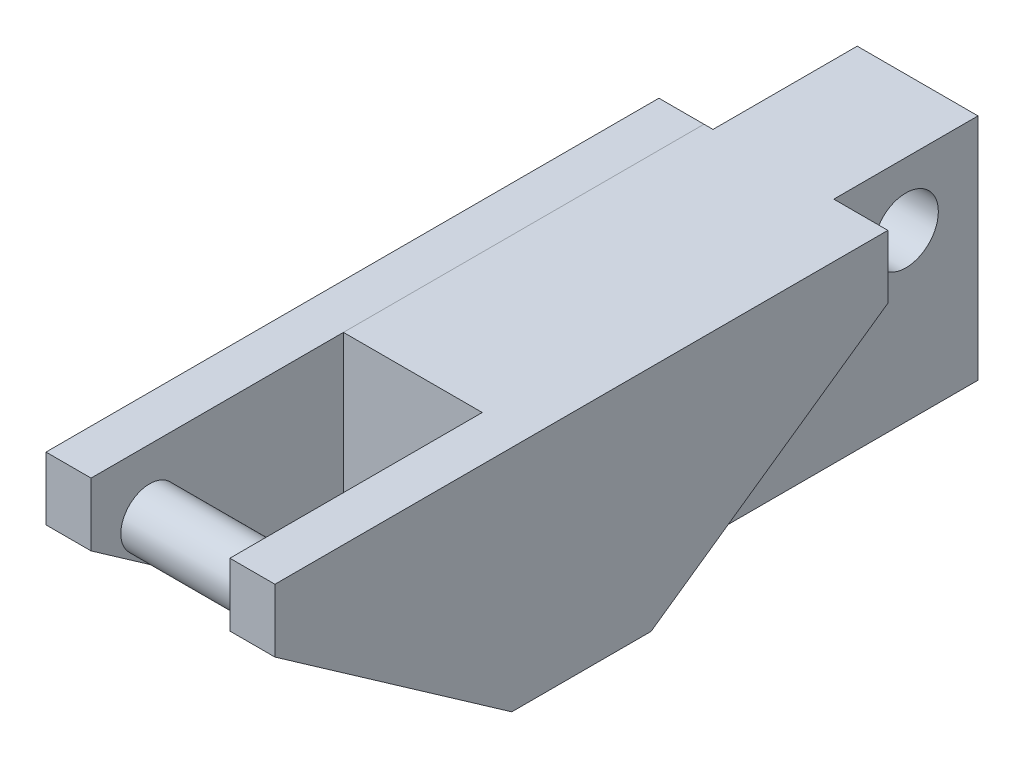
SolidWorks part; units mm, degrees
ref_plane "Front Plane" through (0, 0, 0) normal (0, 0, 1) x (1, 0, 0)
ref_plane "Top Plane" through (0, 0, 0) normal (0, 1, 0) x (1, 0, 0)
ref_plane "Right Plane" through (0, 0, 0) normal (1, 0, 0) x (0, 0, -1)
sketch "Sketch2" plane through (0, 0, 0) normal (0, 1, 0) x (1, 0, 0)
  line L0 (-31.2782, 15.5442) -> (-18.5782, 15.5442)
  line L1 (-28.2782, 23.5442) -> (-21.5782, 23.5442)
  line L2 (-31.2782, 15.5442) -> (-31.2782, -18.4558)
  line L3 (-31.2782, -18.4558) -> (-28.7782, -18.4558)
  line L4 (-18.5782, 15.5442) -> (-18.5782, -18.4558)
  line L5 (-28.2782, 23.5442) -> (-28.2782, 15.5442)
  line L6 (-21.5782, 23.5442) -> (-21.5782, 15.5442)
  line L7 (-28.7782, -18.4558) -> (-28.7782, -4.4558)
  line L8 (-28.7782, -4.4558) -> (-21.0782, -4.4558)
  line L9 (-21.0782, -4.4558) -> (-21.0782, -18.4558)
  line L10 (-31.2782, -4.4558) -> (-18.5782, -4.4558)
  line L11 (-21.0782, -18.4558) -> (-18.5782, -18.4558)
  line L12 (-28.2782, 15.5442) -> (-21.5782, 15.5442)
  dimension "D1" = 42
  dimension "D2" = 12.7
  dimension "D3" = 2.5
  dimension "D4" = 2.5
  dimension "D5" = 3
  dimension "D6" = 3
  dimension "D7" = 8
  dimension "D8" = 14
extrude "Boss-Extrude1" add sketch "Sketch2" along normal blind 12.7 contours L2 L10 L8 L4 L0 | L6 L1 L5 L0 | L9 L11 L4 L10 | L10 L2 L3 L7 region at (-24.9282, 0, -5.5442) region at (-24.9282, 0, -19.5442) region at (-30.0282, 0, 11.4558) region at (-19.8282, 0, 11.4558)
sketch "Sketch3" plane through (0, 0, 0) normal (1, 0, 0) x (0, 0, -1)
  line L0 (-15.2058, 12.7) -> (-15.2058, 0) construction
  line L1 (15.5442, 12.7) -> (-18.4558, 12.7) construction
  line L2 (15.5442, 0) -> (-18.4558, 0) construction
  line L3 (-18.4558, 12.7) -> (-18.4558, 0) construction
  line L4 (-20.9558, 9.2) -> (22.2242, 9.2) construction
  line L5 (23.5442, 12.7) -> (23.5442, 0) construction
  line L6 (19.5442, 12.7) -> (19.5442, 0) construction
  line L7 (23.5442, 12.7) -> (15.5442, 12.7) construction
  line L8 (23.5442, 0) -> (15.5442, 0) construction
  line L9 (-15.2058, 8.1) -> (-15.2058, 4.6) construction
  circle A0 centre (-15.2058, 9.2) radius 1.6
  circle A1 centre (19.5442, 9.2) radius 1.8
  dimension "D3" = 3.5
  dimension "D1" = 3.25
  dimension "D2" = 4
extrude "Cut-Extrude1" cut sketch "Sketch3" against normal through all contours A1
extrude "Boss-Extrude4" add sketch "Sketch3<3>" against normal up to next from surface contours A0 starting at face at (-21.0782, 6.35, 11.4558)
sketch "Sketch3<3>" plane through (0, 0, 0) normal (1, 0, 0) x (0, 0, -1) same geometry as "Sketch3"
sketch "Sketch37" plane through (0, 0, 0) normal (0, -1, 0) x (1, 0, 0)
  line L0 (-24.9282, 4.4558) -> (-24.9282, -23.5442) construction
  line L1 (-28.7782, 4.4558) -> (-21.0782, 4.4558) construction
  line L2 (-28.2782, -23.5442) -> (-21.5782, -23.5442) construction
  line L3 (-23.3282, 4.4558) -> (-24.9282, 4.4558)
  line L4 (-25.7282, 4.4558) -> (-23.3282, 4.4558)
  line L6 (-25.7282, -23.5442) -> (-23.3282, -23.5442)
  line L7 (-23.3282, 4.4558) -> (-23.3282, -23.5442)
  line L8 (-24.9282, 4.4558) -> (-24.9282, -23.5442)
  line L9 (-24.9282, -23.5442) -> (-23.3282, -23.5442)
  dimension "D2" = 1.6
sketch "Sketch38" plane through (-18.5782, 0, 0) normal (1, 0, 0) x (0, 0, -1)
  line L0 (-1.4558, 12.7) -> (-1.4558, 0) construction
  line L1 (15.5442, 12.7) -> (-18.4558, 12.7) construction
  line L2 (15.5442, 0) -> (-18.4558, 0) construction
  line L3 (2.4052, 12.7) -> (2.4052, 0) construction
  line L4 (19.5442, 9.2) -> (-18.4558, 9.2) construction
  line L5 (2.4052, 0) -> (15.5442, 0)
  line L6 (-18.4558, 12.7) -> (-18.4558, 0) construction
  line L7 (15.5442, 12.7) -> (15.5442, 0) construction
  line L14 (15.5442, 0) -> (15.5442, 9.2)
  line L16 (15.5442, 9.2) -> (2.4052, 0)
  line L17 (-5.3168, 0) -> (-18.4558, 0)
  line L18 (-18.4558, 0) -> (-18.4558, 9.2)
  line L19 (-18.4558, 9.2) -> (-5.3168, 0)
  dimension "D1" = 55
extrude "Cut-Extrude19" cut sketch "Sketch38" against normal blind 3 contours L17 L18 L19 | L16 L5 L14
sketch "Sketch39" plane through (0, 12.7, 0) normal (0, 1, 0) x (1, 0, 0)
  line L0 (-24.9282, 23.5442) -> (-24.9282, -16.8058) construction
  line L1 (-28.2782, 23.5442) -> (-21.5782, 23.5442) construction
  line L2 (-28.7782, -16.8058) -> (-21.0782, -16.8058) construction
  line L3 (-24.9282, 23.5442) -> (-24.9282, -16.8058)
sketch "Sketch40" plane through (0, 0, 0) normal (0, 1, 0) x (1, 0, 0)
  line L0 (-24.9282, 23.5442) -> (-24.9282, -16.8058) construction
  line L1 (-24.9282, 23.5442) -> (-24.9282, -16.8058)
sketch "Sketch42" plane through (0, 12.7, 0) normal (0, 1, 0) x (1, 0, 0)
  line L0 (-31.2782, 8.4542) -> (-18.5782, 8.4542) construction
  line L1 (-31.2782, 15.5442) -> (-31.2782, -18.4558) construction
  line L2 (-18.5782, 15.5442) -> (-18.5782, -18.4558) construction
  dimension "D1" = 15.09
ref_plane "Plane1" through (0, 0, -8.4542) normal (0, 0, -1) x (1, 0, 0)
ref_plane "Plane3" through (-24.9282, 0, 0) normal (-1, 0, 0) x (0, 0, 1)
mirror "Mirror10" about plane through (-24.9282, 0, 0) normal (-1, 0, 0) of "Cut-Extrude19"
sketch "Sketch44" plane through (0, 12.7, 0) normal (0, 1, 0) x (1, 0, 0)
  line L0 (-21.0782, -18.4558) -> (-21.0782, 15.5442)
  line L1 (-21.5782, 15.5442) -> (-18.5782, 15.5442) construction
sketch "Sketch45" plane through (0, 12.7, 0) normal (0, 1, 0) x (1, 0, 0)
  line L0 (-28.7782, -18.4558) -> (-28.7782, 15.5442)
  line L1 (-31.2782, 15.5442) -> (-28.2782, 15.5442) construction
split "Split1" trim tools "Sketch45" bodies to split 145 resulting bodies 154 155
sketch "Sketch48" plane through (-18.5782, 0, 0) normal (1, 0, 0) x (0, 0, -1)
  line L0 (2.5442, 12.7) -> (2.5442, 0) construction
  line L3 (-18.4558, 12.7) -> (-18.4558, 9.2) construction
  dimension "D1" = 21
equation "\"0..25in\"=0.2"
